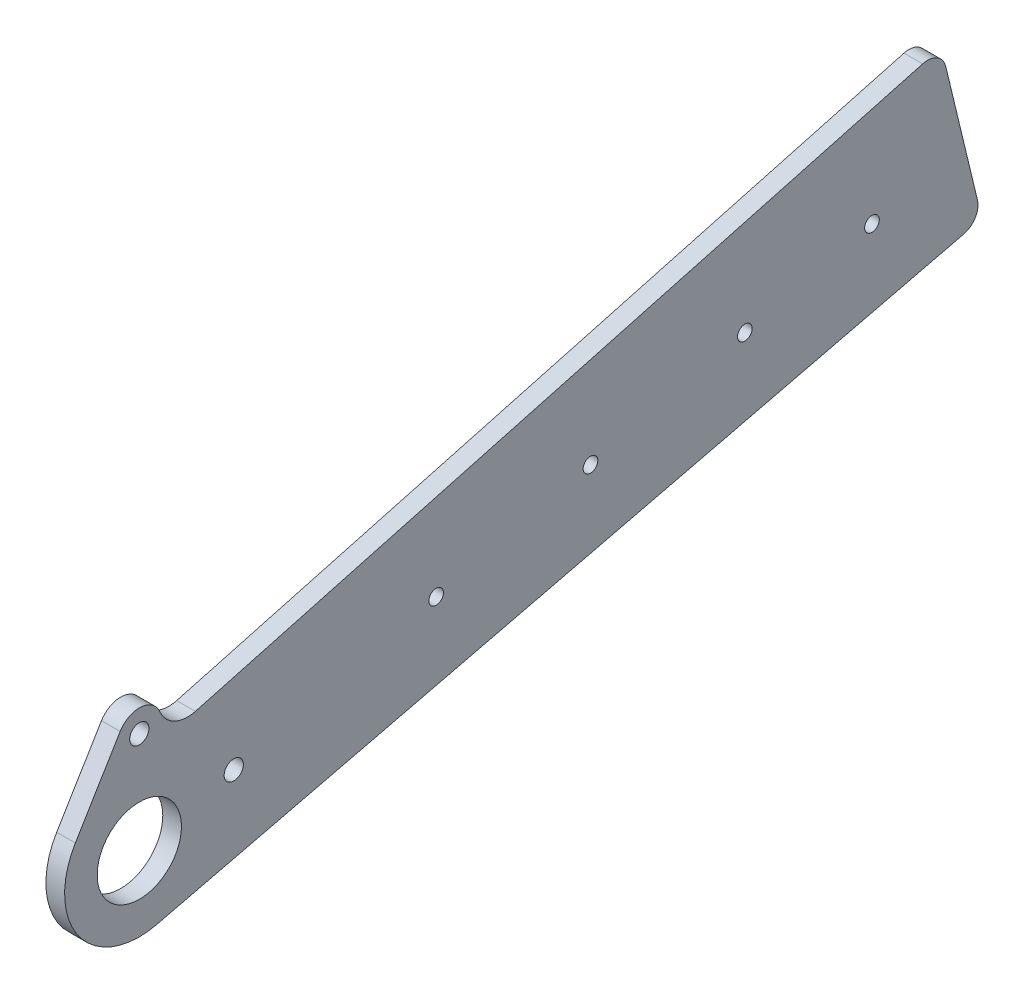
SolidWorks part; units mm, degrees
ref_plane "Alzado" through (0, 0, 0) normal (0, 0, 1) x (1, 0, 0)
ref_plane "Planta" through (0, 0, 0) normal (0, 1, 0) x (1, 0, 0)
ref_plane "Vista lateral" through (0, 0, 0) normal (1, 0, 0) x (0, 0, -1)
sketch "Croquis1" plane through (0, 0, 0) normal (0, 1, 0) x (1, 0, 0)
  line L1 (-101.6, -12.7) -> (101.6, -12.7)
  line L2 (-101.6, -12.7) -> (-101.6, 12.7)
  line L3 (-101.6, 12.7) -> (101.6, 12.7)
  line L4 (101.6, -12.7) -> (101.6, 12.7)
  line L5 (-101.6, -12.7) -> (101.6, 12.7) construction
  line L6 (-101.6, 12.7) -> (101.6, -12.7) construction
  point P0 (0, 0)
  dimension "D1" = 25.4
  dimension "D2" = 203.2
extrude "Saliente-Extruir1" add sketch "Croquis1" along normal blind 25.4
shell "Vaciado1" thickness 3.175 removed face at (-101.6, 12.7, 0) removed face at (101.6, 12.7, 0)
sketch "Croquis2" plane through (0, 25.4, 0) normal (0, 1, 0) x (1, 0, 0)
  line L0 (101.6, 12.7) -> (-101.6, 12.7) construction
  line L1 (-25.4, -12.7) -> (25.4, -12.7)
  line L2 (-25.4, -12.7) -> (-25.4, 12.7)
  line L3 (-25.4, 12.7) -> (25.4, 12.7)
  line L4 (25.4, -12.7) -> (25.4, 12.7)
  line L5 (-25.4, -12.7) -> (25.4, 12.7) construction
  line L6 (-25.4, 12.7) -> (25.4, -12.7) construction
  line L8 (-22.225, -9.525) -> (22.225, -9.525)
  line L9 (-22.225, -9.525) -> (-22.225, 9.525)
  line L10 (-22.225, 9.525) -> (22.225, 9.525)
  line L11 (22.225, -9.525) -> (22.225, 9.525)
  line L12 (-22.225, -9.525) -> (22.225, 9.525) construction
  line L13 (-22.225, 9.525) -> (22.225, -9.525) construction
  point P0 (0, 0)
  point P8 (0, 0)
  dimension "D1" = 50.8
  dimension "D2" = 3.175
  dimension "D3" = 3.175
extrude "Saliente-Extruir2" add sketch "Croquis2" along normal blind 247.65 separate body
sketch "Croquis3" plane through (0, 25.4, 0) normal (0, 1, 0) x (1, 0, 0)
  line L0 (0, 0) -> (0, 12.7) construction
  line L1 (25.4, 12.7) -> (-25.4, 12.7) construction
  circle A0 centre (-47.625, 0) radius 3.2639
  circle A1 centre (-79.375, 0) radius 3.2639
  circle A2 centre (79.375, 0) radius 3.2639
  circle A3 centre (47.625, 0) radius 3.2639
  dimension "D1" = 47.625
  dimension "D2" = 6.5278
  dimension "D3" = 31.75
extrude "Cortar-Extruir1" cut sketch "Croquis3" against normal through all
sketch "Croquis4" plane through (0, 0, 12.7) normal (0, 0, 1) x (1, 0, 0)
  line L0 (0, 25.4) -> (0, 139.6619) construction
  line L1 (-101.6, 25.4) -> (101.6, 25.4) construction
  line L2 (0, 139.6619) -> (-23.8125, 139.6619) construction
  circle A0 centre (0, 139.6619) radius 14.3129
  circle A1 centre (0, 139.6619) radius 23.8125 construction
  circle A2 centre (-23.8125, 139.6619) radius 2.4892 construction
  circle A3 centre (-11.9062, 160.2841) radius 2.4892
  circle A4 centre (11.9063, 160.2841) radius 2.4892
  circle A5 centre (23.8125, 139.6619) radius 2.4892 construction
  circle A6 centre (11.9062, 119.0397) radius 2.4892
  circle A7 centre (-11.9063, 119.0397) radius 2.4892
  dimension "D1" = 28.6258
  dimension "D3" = 47.625
  dimension "D4" = 4.9784
  dimension "D2" = 114.2619
  dimension "D6" = 23.8125
  dimension "D5" = 6
extrude "Cortar-Extruir2" cut sketch "Croquis4" against normal through all
sketch "Croquis8" plane through (0, 0, 12.7) normal (0, 0, 1) x (1, 0, 0)
  line L0 (0, 0) -> (0, 273.05) construction
  line L1 (-101.6, 12.7) -> (0, 12.7) construction
  line L2 (-101.6, 25.4) -> (-101.6, 0) construction
  line L3 (0, 12.7) -> (-12.7, 12.7) construction
  line L4 (0, 12.7) -> (12.7, 12.7) construction
  line L5 (-25.4, 273.05) -> (25.4, 273.05) construction
  line L6 (-12.7, 12.7) -> (-12.7, 25.4) construction
  circle A0 centre (0, 12.7) radius 2.4892
  circle A1 centre (-12.7, 12.7) radius 2.4892
  circle A2 centre (-25.4, 12.7) radius 2.4892
  circle A3 centre (-38.1, 12.7) radius 2.4892
  circle A4 centre (-50.8, 12.7) radius 2.4892
  circle A5 centre (0, 12.7) radius 2.4892
  circle A6 centre (-12.7, 12.7) radius 2.4892
  circle A7 centre (-25.4, 12.7) radius 2.4892
  circle A8 centre (-38.1, 12.7) radius 2.4892
  circle A9 centre (12.7, 12.7) radius 2.4892
  circle A10 centre (0, 12.7) radius 2.4892
  circle A11 centre (-12.7, 12.7) radius 2.4892
  circle A12 centre (-25.4, 12.7) radius 2.4892
  circle A13 centre (25.4, 12.7) radius 2.4892
  circle A14 centre (12.7, 12.7) radius 2.4892
  circle A15 centre (0, 12.7) radius 2.4892
  circle A16 centre (-12.7, 12.7) radius 2.4892
  circle A17 centre (38.1, 12.7) radius 2.4892
  circle A18 centre (25.4, 12.7) radius 2.4892
  circle A19 centre (12.7, 12.7) radius 2.4892
  circle A20 centre (0, 12.7) radius 2.4892
  circle A21 centre (12.7, 12.7) radius 2.4892
  circle A22 centre (25.4, 12.7) radius 2.4892
  circle A23 centre (38.1, 12.7) radius 2.4892
  circle A24 centre (50.8, 12.7) radius 2.4892
  circle A25 centre (-12.7, 25.4) radius 2.4892 [skipped]
  circle A26 centre (12.7, 25.4) radius 2.4892 [skipped]
  circle A27 centre (-12.7, 38.1) radius 2.4892
  circle A28 centre (12.7, 38.1) radius 2.4892
  circle A29 centre (-12.7, 50.8) radius 2.4892
  circle A30 centre (12.7, 50.8) radius 2.4892
  circle A31 centre (-12.7, 63.5) radius 2.4892
  circle A32 centre (12.7, 63.5) radius 2.4892
  circle A33 centre (-12.7, 76.2) radius 2.4892
  circle A34 centre (12.7, 76.2) radius 2.4892
  dimension "D1" = 4.9784
  dimension "D4" = 12.7
  dimension "D5" = 12.7
  dimension "D7" = 12.7
  dimension "D2" = 5
  dimension "D3" = 5
  dimension "D6" = 6
extrude "Cortar-Extruir4" cut sketch "Croquis8" against normal through all contours A4 | A3 | A2 | A1 | A0 | A9 | A13 | A17 | A24 | A28 | A29 | A30 | A31 | A32 | A34 | A33 | A27 region at (0, 12.7, 12.7) region at (-12.7, 12.7, 12.7) region at (-25.4, 12.7, 12.7) region at (-38.1, 12.7, 12.7) region at (-50.8, 12.7, 12.7) region at (12.7, 12.7, 12.7) region at (25.4, 12.7, 12.7) region at (38.1, 12.7, 12.7) region at (50.8, 12.7, 12.7) region at (12.7, 38.1, 12.7) region at (-12.7, 50.8, 12.7) region at (12.7, 50.8, 12.7) region at (-12.7, 63.5, 12.7) region at (12.7, 63.5, 12.7) region at (-12.7, 76.2, 12.7) region at (12.7, 76.2, 12.7)
sketch "Croquis6" plane through (0, 0, 12.7) normal (0, 0, 1) x (1, 0, 0)
  line L0 (25.4, 273.05) -> (25.4, 25.4) construction
  line L1 (-25.4, 88.646) -> (25.4, 88.646)
  line L2 (-25.4, 88.646) -> (-25.4, 114.046)
  line L3 (-25.4, 114.046) -> (25.4, 114.046)
  line L4 (25.4, 88.646) -> (25.4, 114.046)
  line L5 (-25.4, 88.646) -> (25.4, 114.046) construction
  line L6 (-25.4, 114.046) -> (25.4, 88.646) construction
  line L7 (-101.6, 25.4) -> (101.6, 25.4) construction
  line L9 (-22.225, 91.821) -> (22.225, 91.821)
  line L10 (-22.225, 91.821) -> (-22.225, 110.871)
  line L11 (-22.225, 110.871) -> (22.225, 110.871)
  line L12 (22.225, 91.821) -> (22.225, 110.871)
  line L13 (-22.225, 91.821) -> (22.225, 110.871) construction
  line L14 (-22.225, 110.871) -> (22.225, 91.821) construction
  point P0 (0, 101.346)
  point P11 (0, 101.346)
  dimension "D1" = 25.4
  dimension "D2" = 63.246
  dimension "D3" = 3.175
  dimension "D4" = 3.175
extrude "Saliente-Extruir3" add sketch "Croquis6" along normal blind 69.85 separate body
sketch "Croquis7" plane through (0, 114.046, 0) normal (0, 1, 0) x (1, 0, 0)
  line L0 (0, -12.7) -> (0, -82.55) construction
  line L1 (-25.4, -12.7) -> (25.4, -12.7) construction
  line L2 (25.4, -82.55) -> (-25.4, -82.55) construction
  line L3 (16.51, -12.7) -> (-16.51, -12.7)
  line L4 (25.4, -12.7) -> (-25.4, -12.7) construction
  line L5 (-16.51, -12.7) -> (-16.51, -34.798)
  line L6 (-13.208, -38.1) -> (13.208, -38.1)
  line L7 (16.51, -12.7) -> (16.51, -34.798)
  arc A0 (16.51, -34.798) -> (13.208, -38.1) centre (13.208, -34.798) cw
  arc A1 (-16.51, -34.798) -> (-13.208, -38.1) centre (-13.208, -34.798) ccw
  point P12 (0, -38.1)
  point P16 (16.51, -38.1)
  point P19 (-16.51, -38.1)
  dimension "D3" = 3.302
  dimension "D1" = 25.4
  dimension "D2" = 33.02
extrude "Cortar-Extruir3" cut sketch "Croquis7" against normal up to next (3.175 mm away)
sketch "Croquis11" plane through (25.4, 0, 0) normal (1, 0, 0) x (0, 0, -1)
  line L0 (0, -101.854) -> (-381, -101.854) construction
  line L1 (-82.55, 88.646) -> (-82.55, 114.046) construction
  line L2 (-82.55, 88.646) -> (-12.7, 88.646) construction
  line L6 (-517.96, -101.854) -> (-276.66, -101.854) construction
  line L7 (-517.96, -101.854) -> (-517.96, 139.446) construction
  line L8 (-517.96, 139.446) -> (-276.66, 139.446) construction
  line L9 (-276.66, -101.854) -> (-276.66, 139.446) construction
  circle A0 centre (-396.875, 145.796) radius 38.1
  dimension "D3" = 76.2
  dimension "D4" = 209.55
  dimension "D5" = 276.225
  dimension "D1" = 190.5
  dimension "D2" = 381
  dimension "D6" = 241.3
sketch "Croquis9" plane through (0, 0, 12.7) normal (0, 0, 1) x (1, 0, 0)
  line L0 (0, 0) -> (0, 273.05) construction
  line L1 (-25.4, 273.05) -> (25.4, 273.05) construction
  line L2 (50.8, 0) -> (-50.8, 0)
  line L3 (-101.6, 0) -> (101.6, 0) construction
  line L4 (-57.15, 6.35) -> (-57.15, 23.7481)
  line L5 (-101.6, 25.4) -> (101.6, 25.4) construction
  line L6 (-56.3451, 26.8425) -> (-27.2168, 79.0403)
  line L7 (-25.4, 273.05) -> (-25.4, 25.4) construction
  line L8 (-21.6717, 82.296) -> (21.6717, 82.296)
  line L9 (56.3451, 26.8425) -> (27.2168, 79.0403)
  line L10 (57.15, 6.35) -> (57.15, 23.7481)
  line L11 (-25.4, 88.646) -> (25.4, 88.646) construction
  circle A0 centre (-50.8, 12.7) radius 2.4892 construction
  arc A2 (-50.8, 0) -> (-57.15, 6.35) centre (-50.8, 6.35) cw
  arc A3 (-57.15, 23.7481) -> (-56.3451, 26.8425) centre (-50.8, 23.7481) cw
  arc A4 (-27.2168, 79.0403) -> (-21.6717, 82.296) centre (-21.6717, 75.946) cw
  arc A5 (27.2168, 79.0403) -> (21.6717, 82.296) centre (21.6717, 75.946) ccw
  arc A6 (57.15, 23.7481) -> (56.3451, 26.8425) centre (50.8, 23.7481) ccw
  arc A7 (50.8, 0) -> (57.15, 6.35) centre (50.8, 6.35) ccw
  circle A9 centre (-25.4, 12.7) radius 2.4892
  circle A10 centre (-25.4, 12.7) radius 2.4892
  circle A11 centre (-12.7, 12.7) radius 2.4892
  circle A12 centre (-12.7, 12.7) radius 2.4892
  circle A13 centre (0, 12.7) radius 2.4892
  circle A14 centre (0, 12.7) radius 2.4892
  circle A15 centre (0, 12.7) radius 2.4892
  circle A16 centre (0, 12.7) radius 2.4892
  circle A17 centre (12.7, 12.7) radius 2.4892
  circle A18 centre (12.7, 12.7) radius 2.4892
  circle A19 centre (-38.1, 12.7) radius 2.4892
  circle A20 centre (-38.1, 12.7) radius 2.4892
  circle A21 centre (-25.4, 12.7) radius 2.4892
  circle A22 centre (-25.4, 12.7) radius 2.4892
  circle A23 centre (-12.7, 12.7) radius 2.4892
  circle A24 centre (-12.7, 12.7) radius 2.4892
  circle A25 centre (0, 12.7) radius 2.4892
  circle A26 centre (0, 12.7) radius 2.4892
  circle A27 centre (-50.8, 12.7) radius 2.4892
  circle A28 centre (-50.8, 12.7) radius 2.4892
  circle A29 centre (-38.1, 12.7) radius 2.4892
  circle A30 centre (-38.1, 12.7) radius 2.4892
  circle A31 centre (25.4, 12.7) radius 2.4892
  circle A32 centre (25.4, 12.7) radius 2.4892
  circle A33 centre (38.1, 12.7) radius 2.4892
  circle A34 centre (38.1, 12.7) radius 2.4892
  circle A35 centre (-12.7, 12.7) radius 2.4892
  circle A36 centre (-12.7, 12.7) radius 2.4892
  circle A37 centre (0, 12.7) radius 2.4892
  circle A38 centre (0, 12.7) radius 2.4892
  circle A39 centre (12.7, 12.7) radius 2.4892
  circle A40 centre (12.7, 12.7) radius 2.4892
  circle A41 centre (25.4, 12.7) radius 2.4892
  circle A42 centre (25.4, 12.7) radius 2.4892
  circle A43 centre (-25.4, 12.7) radius 2.4892
  circle A44 centre (-25.4, 12.7) radius 2.4892
  circle A45 centre (-12.7, 12.7) radius 2.4892
  circle A46 centre (-12.7, 12.7) radius 2.4892
  circle A47 centre (50.8, 12.7) radius 2.4892
  circle A48 centre (50.8, 12.7) radius 2.4892
  circle A49 centre (38.1, 12.7) radius 2.4892
  circle A50 centre (38.1, 12.7) radius 2.4892
  circle A51 centre (25.4, 12.7) radius 2.4892
  circle A52 centre (25.4, 12.7) radius 2.4892
  circle A53 centre (12.7, 12.7) radius 2.4892
  circle A54 centre (12.7, 12.7) radius 2.4892
  circle A55 centre (0, 12.7) radius 2.4892
  circle A56 centre (0, 12.7) radius 2.4892
  circle A57 centre (12.7, 12.7) radius 2.4892
  circle A58 centre (12.7, 12.7) radius 2.4892
  circle A59 centre (-12.7, 76.2) radius 2.4892
  circle A60 centre (-12.7, 76.2) radius 2.4892
  circle A61 centre (12.7, 63.5) radius 2.4892
  circle A62 centre (12.7, 63.5) radius 2.4892
  circle A63 centre (-12.7, 63.5) radius 2.4892
  circle A64 centre (-12.7, 63.5) radius 2.4892
  circle A65 centre (12.7, 50.8) radius 2.4892
  circle A66 centre (12.7, 50.8) radius 2.4892
  circle A67 centre (-12.7, 50.8) radius 2.4892
  circle A68 centre (-12.7, 50.8) radius 2.4892
  circle A69 centre (12.7, 38.1) radius 2.4892
  circle A70 centre (12.7, 38.1) radius 2.4892
  circle A71 centre (-12.7, 38.1) radius 2.4892
  circle A72 centre (-12.7, 38.1) radius 2.4892
  circle A73 centre (12.7, 76.2) radius 2.4892
  circle A74 centre (12.7, 76.2) radius 2.4892
  point P22 (-57.15, 0)
  point P25 (-57.15, 25.4)
  point P28 (-25.4, 82.296)
  point P38 (0, 82.296)
  dimension "D1" = 6.35
  dimension "D3" = 6.35
  dimension "D37" = 6.35
  dimension "D4" = 0
  dimension "D5" = 0
  dimension "D6" = 0
  dimension "D7" = 0
  dimension "D8" = 0
  dimension "D9" = 0
  dimension "D10" = 0
  dimension "D11" = 0
  dimension "D12" = 0
  dimension "D13" = 0
  dimension "D14" = 0
  dimension "D15" = 0
  dimension "D16" = 0
  dimension "D17" = 0
  dimension "D18" = 0
  dimension "D19" = 0
  dimension "D20" = 0
  dimension "D21" = 0
  dimension "D22" = 0
  dimension "D23" = 0
  dimension "D24" = 0
  dimension "D25" = 0
  dimension "D26" = 0
  dimension "D27" = 0
  dimension "D28" = 0
  dimension "D29" = 0
  dimension "D30" = 0
  dimension "D31" = 0
  dimension "D32" = 0
  dimension "D33" = 0
  dimension "D34" = 0
  dimension "D35" = 0
  dimension "D36" = 0
extrude "Saliente-Extruir4" add sketch "Croquis9" along normal blind 6.35 separate body contours L0 L8 A4 L6 A3 A60 A64 A68 A72 | L0 A6 L9 A5 L8 A74 A70 A66 A62 | L0 A3 L4 A2 | L0 L2 A7 L10 A6 A56 region at (-24.3725, 36.0328, 12.7) region at (24.3725, 36.0328, 12.7)
sketch "Croquis15" plane through (25.4, 0, 0) normal (1, 0, 0) x (0, 0, -1)
  line L0 (-12.7, 0) -> (-12.7, 171.1325) construction
  line L1 (-12.7, 273.05) -> (-12.7, 25.4) construction
  line L2 (-72.5746, 227.1642) -> (-41.5317, 154.1315) construction
  line L3 (-105.4538, 208.2656) -> (-57.9713, 144.6822) construction
  line L4 (-94.6246, 238.2605) -> (-401.3483, 164.3633) construction
  line L5 (-392.4017, 127.2287) -> (-85.6779, 201.1258) construction
  line L8 (-82.55, 114.046) -> (-12.7, 114.046) construction
  circle A0 centre (-50.32, 150.396) radius 30
  arc A1 (-57.9713, 144.6822) -> (-41.5317, 154.1315) centre (-50.32, 150.396) ccw construction
  arc A2 (-401.3483, 164.3633) -> (-392.4017, 127.2287) centre (-396.875, 145.796) ccw construction
  arc A3 (-72.5746, 227.1642) -> (-105.4538, 208.2656) centre (-90.1513, 219.6932) ccw construction
  arc A4 (-85.6779, 201.1258) -> (-94.6246, 238.2605) centre (-90.1513, 219.6932) ccw construction
  dimension "D2" = 60
  dimension "D3" = 19.0986
  dimension "D4" = 38.1972
  dimension "D1" = 171.1325
  dimension "D7" = 6.35
  dimension "D8" = 7.62
sketch "Croquis16" plane through (25.4, 0, 0) normal (1, 0, 0) x (0, 0, -1)
  line L0 (-50.32, 150.396) -> (-50.32, 175.796) construction
  line L1 (-13.4332, 272.8734) -> (-118.1525, 247.644)
  line L2 (-82.55, 94.996) -> (-82.55, 113.9625)
  line L3 (-82.5522, 114.1295) -> (-83.4835, 149.5234)
  line L4 (-76.2, 88.646) -> (6.35, 88.646)
  line L5 (12.7, 273.05) -> (12.7, 25.4) construction
  line L6 (12.7, 94.996) -> (12.7, 266.7)
  line L7 (6.35, 273.05) -> (-11.9459, 273.05)
  line L8 (-94.6246, 238.2605) -> (-401.3483, 164.3633) construction
  line L9 (-122.8385, 239.9833) -> (-110.0117, 186.743)
  line L10 (-90.1513, 219.6932) -> (-116.4251, 213.3632) construction
  circle A0 centre (-90.1513, 219.6932) radius 14.3256
  circle A1 centre (-50.32, 150.396) radius 33.175
  circle A4 centre (-50.32, 150.396) radius 9.5631
  circle A5 centre (-50.32, 150.396) radius 25.4 construction
  circle A6 centre (-50.32, 175.796) radius 2.4892
  circle A7 centre (-32.3595, 168.3565) radius 2.4892 construction
  circle A8 centre (-24.92, 150.396) radius 2.4892
  circle A9 centre (-32.3595, 132.4355) radius 2.4892
  circle A10 centre (-50.32, 124.996) radius 2.4892
  circle A11 centre (-68.2805, 132.4355) radius 2.4892
  circle A12 centre (-75.72, 150.396) radius 2.4892
  circle A13 centre (-68.2805, 168.3565) radius 2.4892
  arc A18 (-105.7366, 182.1707) -> (-83.4864, 151.1506) centre (-115.2282, 151.8727) cw
  arc A19 (-110.0117, 186.743) -> (-105.7366, 182.1707) centre (-103.8383, 188.2304) ccw
  arc A21 (-118.1525, 247.644) -> (-122.8385, 239.9833) centre (-116.6652, 241.4706) ccw
  arc A23 (-11.9459, 273.05) -> (-13.4332, 272.8734) centre (-11.9459, 266.7) ccw
  circle A26 centre (-50.32, 150.396) radius 30 construction
  arc A29 (-82.55, 113.9625) -> (-82.5522, 114.1295) centre (-88.9, 113.9625) ccw
  arc A31 (12.7, 266.7) -> (6.35, 273.05) centre (6.35, 266.7) ccw
  arc A32 (6.35, 88.646) -> (12.7, 94.996) centre (6.35, 94.996) ccw
  arc A33 (-82.55, 94.996) -> (-76.2, 88.646) centre (-76.2, 94.996) ccw
  point P45 (-12.7, 273.05)
  point P72 (-82.55, 114.046)
  point P74 (12.7, 273.05)
  point P77 (12.7, 88.646)
  point P80 (-82.55, 88.646)
  dimension "D1" = 28.6512
  dimension "D2" = 3.175
  dimension "D3" = 31.75
  dimension "D4" = 19.1262
  dimension "D5" = 50.8
  dimension "D6" = 4.9784
  dimension "D9" = 6.35
  dimension "D10" = 6.35
  dimension "D14" = 6.35
  dimension "D15" = 6.35
  dimension "D12" = 6.35
  dimension "D8" = 25.4
  dimension "D11" = 12.7
  dimension "D7" = 8
extrude "Saliente-Extruir5" add sketch "Croquis16" along normal blind 6.35 separate body contours L4 A32 A31 A23 | L2 A33 L4 A23 L1 A21 L9 A19 A18 A1 L3 A29 A0 | A1 A13 A12 A11 A10 A9 A8 A6 A4 region at (25.4, 188.5949, 38.9873) region at (25.4, 182.6306, 49.9534)
sketch "Croquis12" plane through (25.4, 0, 0) normal (1, 0, 0) x (0, 0, -1)
  line L0 (-82.55, 101.346) -> (-12.7, 101.346) construction
  line L1 (-82.55, 88.646) -> (-82.55, 114.046) construction
  line L2 (-12.7, 88.646) -> (-12.7, 114.046) construction
  line L3 (0, 273.05) -> (0, 0) construction
  line L4 (-12.7, 273.05) -> (12.7, 273.05) construction
  line L5 (0, 101.346) -> (-12.7, 101.346) construction
  line L6 (0, 101.346) -> (0, 114.046) construction
  circle A1 centre (0, 101.346) radius 2.4892
  circle A2 centre (-12.7, 101.346) radius 2.4892 [skipped]
  circle A3 centre (-25.4, 101.346) radius 2.4892
  circle A4 centre (-38.1, 101.346) radius 2.4892
  circle A5 centre (-50.8, 101.346) radius 2.4892
  circle A6 centre (0, 114.046) radius 2.4892
  circle A7 centre (0, 126.746) radius 2.4892
  circle A8 centre (0, 139.446) radius 2.4892
  circle A9 centre (0, 152.146) radius 2.4892
  circle A10 centre (0, 164.846) radius 2.4892
  circle A11 centre (0, 177.546) radius 2.4892
  circle A12 centre (0, 190.246) radius 2.4892
  circle A13 centre (0, 202.946) radius 2.4892
  circle A14 centre (0, 215.646) radius 2.4892
  circle A15 centre (0, 228.346) radius 2.4892
  circle A16 centre (0, 241.046) radius 2.4892
  circle A17 centre (0, 253.746) radius 2.4892
  circle A18 centre (0, 266.446) radius 2.4892
  circle A19 centre (-63.5, 101.346) radius 2.4892
  circle A20 centre (-76.2, 101.346) radius 2.4892
  dimension "D1" = 4.9784
  dimension "D3" = 12.7
  dimension "D5" = 12.7
  dimension "D2" = 7
  dimension "D4" = 14
extrude "Cortar-Extruir5" cut sketch "Croquis12" against normal through all and the other way through all
sketch "Croquis17" plane through (31.75, 0, 0) normal (1, 0, 0) x (0, 0, -1)
  line L0 (-403.5186, 170.3118) -> (-118.2389, 247.6205)
  line L1 (-118.0654, 247.6649) -> (-21.2705, 270.9852)
  line L2 (-390.9258, 121.1026) -> (-118.1525, 186.8202)
  line L3 (-392.4017, 127.2287) -> (-85.6779, 201.1258) construction
  line L4 (-118.1525, 186.8202) -> (-112.4025, 188.2055)
  line L5 (-13.4332, 206.3797) -> (-13.4332, 264.8118)
  line L7 (-403.3993, 184.1476) -> (-418.6226, 158.9186)
  circle A0 centre (-396.875, 145.796) radius 14.3256
  circle A1 centre (-90.1513, 219.6932) radius 14.3256
  circle A2 centre (-396.875, 145.796) radius 25.4
  arc A3 (-118.2389, 247.6205) -> (-118.0654, 247.6649) centre (-116.578, 241.4916) cw
  arc A4 (-21.2705, 270.9852) -> (-13.4332, 264.8118) centre (-19.7832, 264.8118) cw
  arc A5 (-13.4332, 206.3797) -> (-43.9384, 181.4981) centre (-38.8332, 206.3797) cw
  circle A6 centre (-50.32, 150.396) radius 31.75
  arc A8 (-110.0117, 186.743) -> (-105.7366, 182.1707) centre (-103.8383, 188.2304) ccw construction
  arc A9 (-110.0117, 186.743) -> (-105.7366, 182.1707) centre (-103.8383, 188.2304) ccw
  arc A10 (-110.0117, 186.743) -> (-112.4025, 188.2055) centre (-111.9383, 186.2789) ccw
  arc A11 (-83.4864, 151.1506) -> (-105.7366, 182.1707) centre (-115.2282, 151.8727) ccw construction
  arc A12 (-89.8175, 170.9084) -> (-105.7366, 182.1707) centre (-115.2282, 151.8727) ccw
  arc A13 (-89.8175, 170.9084) -> (-74.8387, 170.5677) centre (-82.1943, 176.6192) ccw
  circle A14 centre (-396.875, 180.2108) radius 7.62
  arc A16 (-389.8471, 183.1558) -> (-377.8191, 177.2761) centre (-380.4766, 187.0824) ccw
  point P19 (-118.1525, 247.644)
  point P23 (-13.4332, 272.8734)
  dimension "D1" = 28.6512
  dimension "D2" = 50.8
  dimension "D3" = 6.35
  dimension "D4" = 63.5
  dimension "D5" = 9.525
  dimension "D6" = 25.4
  dimension "D7" = 15.24
  dimension "D8" = 34.4148
  dimension "D9" = 10.16
extrude "Saliente-Extruir6" add sketch "Croquis17" along normal blind 6.35 separate body contours A2 L2 L0 | L5 A4 A3 L0 | A2 A0 | A16 A14 L7 A2 L0 | A14 region at (31.75, 173.536, 401.4081) region at (31.75, 197.0567, 182.132) region at (31.75, 165.3985, 381.8776) region at (31.75, 180.2108, 396.875)
sketch "Croquis18" plane through (38.1, 0, 0) normal (1, 0, 0) x (0, 0, -1)
  line L0 (-122.8385, 239.9833) -> (-110.0117, 186.743) construction
  line L1 (-122.754, 239.6323) -> (-111.9631, 194.8431)
  line L2 (-403.5186, 170.3118) -> (-118.2389, 247.6205) construction
  line L3 (-403.3993, 184.1476) -> (-418.6226, 158.9186) construction
  line L5 (-403.3993, 184.1476) -> (-418.6226, 158.9186)
  line L6 (-390.9258, 121.1026) -> (-118.1525, 186.8202) construction
  line L7 (-403.5186, 170.3118) -> (-130.5882, 244.274)
  line L10 (-122.8385, 239.9833) -> (-110.0117, 186.743) construction
  line L11 (-390.9258, 121.1026) -> (-116.6492, 187.1824)
  circle A1 centre (-396.875, 145.796) radius 25.4
  circle A2 centre (-396.875, 145.796) radius 25.4
  arc A3 (-116.6492, 187.1824) -> (-111.9631, 194.8431) centre (-118.1365, 193.3558) ccw
  circle A5 centre (-396.875, 145.796) radius 14.3256
  circle A6 centre (-396.875, 145.796) radius 14.3256
  arc A12 (-122.754, 239.6323) -> (-130.5882, 244.274) centre (-128.9273, 238.145) ccw
  arc A13 (-389.8471, 183.1558) -> (-377.8191, 177.2761) centre (-380.4766, 187.0824) ccw construction
  circle A14 centre (-396.875, 180.2108) radius 7.62 construction
  arc A15 (-389.8471, 183.1558) -> (-377.8191, 177.2761) centre (-380.4766, 187.0824) ccw
  circle A16 centre (-396.875, 180.2108) radius 7.62
  point P18 (-110.4758, 188.6697)
  dimension "D2" = 6.35
  dimension "D1" = 0
  dimension "D3" = 0
extrude "Saliente-Extruir7" add sketch "Croquis18" along normal blind 6.35 from surface separate body contours L1 A12 A2 A3 | A2 | A16 A2 L7 | A16 region at (38.1, 184.7417, 244.7476) region at (38.1, 173.536, 401.4081) region at (38.1, 131.2122, 416.7871) region at (38.1, 180.2108, 396.875) starting at face at (25.4, 101.346, -2.4892)
sketch "Croquis22" plane through (38.1, 0, 0) normal (1, 0, 0) x (0, 0, -1)
  line L0 (-396.875, 145.796) -> (-90.1513, 219.6932) construction
  line L1 (-90.1513, 219.6932) -> (-50.32, 150.396) construction
  line L4 (-50.32, 236.121) -> (-37.62, 236.121) construction
  line L5 (-21.2705, 270.9852) -> (-118.0654, 247.6649) construction
  circle A0 centre (-396.875, 180.2108) radius 3.2639
  circle A1 centre (-364.7735, 153.53) radius 3.2639
  circle A2 centre (-396.875, 145.796) radius 19.0986 construction
  arc A3 (-401.3483, 164.3633) -> (-392.4017, 127.2287) centre (-396.875, 145.796) ccw construction
  circle A4 centre (-364.7735, 153.53) radius 6.35 construction
  circle A7 centre (-72.747, 189.4137) radius 3.2639
  circle A8 centre (-72.747, 189.4137) radius 6.35 construction
  circle A9 centre (-50.32, 213.896) radius 6.35 construction
  circle A10 centre (-50.32, 213.896) radius 3.2639
  circle A13 centre (-37.62, 236.121) radius 3.2639
  circle A14 centre (-37.62, 236.121) radius 6.35 construction
  circle A15 centre (-72.747, 252.0515) radius 3.2639
  circle A16 centre (-72.747, 252.0515) radius 6.35 construction
  circle A17 centre (-19.7832, 264.8118) radius 6.35 construction
  circle A18 centre (-19.7832, 264.8118) radius 3.2639
  dimension "D1" = 6.5278
  dimension "D2" = 33.02
  dimension "D3" = 12.7
  dimension "D4" = 34.925
  dimension "D5" = 63.5
  dimension "D6" = 22.225
  dimension "D7" = 12.7
extrude "Cortar-Extruir6" cut sketch "Croquis22" against normal through all
sketch "Croquis24" plane through (38.1, 0, 0) normal (1, 0, 0) x (0, 0, -1)
  line L0 (-396.875, 145.796) -> (-90.1513, 219.6932) construction
  line L1 (-243.5131, 182.7446) -> (-247.9864, 201.3119) construction
  line L2 (-94.6246, 238.2605) -> (-401.3483, 164.3633) construction
  circle A0 centre (-295.9867, 170.1024) radius 2.4892
  circle A1 centre (-191.0395, 195.3867) radius 2.4892
  circle A2 centre (-243.5131, 182.7446) radius 2.4892
  circle A3 centre (-147.826, 205.7979) radius 2.4892
  dimension "D1" = 4.9784
  dimension "D2" = 53.975
  dimension "D3" = 44.45
sketch "Croquis25" plane through (31.75, 0, 0) normal (1, 0, 0) x (0, 0, -1)
  line L0 (-12.7, 0) -> (-12.7, 139.7) construction
  line L1 (-12.7, 123.825) -> (-12.7, 155.575)
  line L2 (-12.7, 0) -> (-12.7, 171.1325) construction
  line L3 (-15.875, 158.75) -> (-17.145, 158.75)
  line L4 (-20.32, 155.575) -> (-20.32, 123.825)
  line L5 (-12.7, 139.7) -> (-20.32, 139.7) construction
  line L6 (-15.875, 120.65) -> (-17.145, 120.65)
  arc A0 (-12.7, 155.575) -> (-15.875, 158.75) centre (-15.875, 155.575) ccw
  arc A1 (-15.875, 120.65) -> (-12.7, 123.825) centre (-15.875, 123.825) ccw
  arc A2 (-17.145, 120.65) -> (-20.32, 123.825) centre (-17.145, 123.825) cw
  arc A3 (-17.145, 158.75) -> (-20.32, 155.575) centre (-17.145, 155.575) ccw
  point P13 (-12.7, 158.75)
  point P16 (-12.7, 120.65)
  point P19 (-20.32, 120.65)
  point P22 (-20.32, 158.75)
  dimension "D4" = 3.175
  dimension "D1" = 139.7
  dimension "D2" = 7.62
  dimension "D3" = 38.1
extrude "Cortar-Extruir8" cut sketch "Croquis25" against normal through all
extrude "Cortar-Extruir9" cut sketch "Croquis24" against normal through all
delete or keep bodies "Sólido-Eliminar/Conservar 1" [suppressed] type keep bodies bodies 112
delete or keep bodies "Sólido-Eliminar/Conservar 2" [suppressed] type keep bodies bodies 111
delete or keep bodies "Sólido-Eliminar/Conservar 3" [suppressed] type keep bodies bodies 107
delete or keep bodies "Sólido-Eliminar/Conservar 4" [suppressed] type keep bodies bodies 109
delete or keep bodies "Sólido-Eliminar/Conservar 5" [suppressed] type keep bodies bodies 121
delete or keep bodies "Sólido-Eliminar/Conservar 6" [suppressed] type keep bodies bodies 125
sketch "Croquis29" plane through (0, 0, 0) normal (1, 0, 0) x (0, 0, -1)
  line L0 (-392.4017, 127.2287) -> (-85.6779, 201.1258) construction
  line L1 (-94.6246, 238.2605) -> (-401.3483, 164.3633) construction
  line L2 (-392.4017, 127.2287) -> (-85.6779, 201.1258) construction
  line L3 (-94.6246, 238.2605) -> (-401.3483, 164.3633) construction
  line L4 (-392.8842, 129.2314) -> (-86.1604, 203.1285)
  line L5 (-94.1421, 236.2578) -> (-400.8658, 162.3606)
  line L6 (-391.9941, 125.5371) -> (-85.2704, 199.4342)
  line L7 (-95.0321, 239.9521) -> (-401.7559, 166.0549)
  arc A0 (-85.6779, 201.1258) -> (-94.6246, 238.2605) centre (-90.1513, 219.6932) ccw construction
  arc A1 (-401.3483, 164.3633) -> (-392.4017, 127.2287) centre (-396.875, 145.796) ccw construction
  arc A2 (-85.6779, 201.1258) -> (-94.6246, 238.2605) centre (-90.1513, 219.6932) ccw construction
  arc A3 (-401.3483, 164.3633) -> (-392.4017, 127.2287) centre (-396.875, 145.796) ccw construction
  arc A4 (-86.1604, 203.1285) -> (-94.1421, 236.2578) centre (-90.1513, 219.6932) ccw
  arc A5 (-400.8658, 162.3606) -> (-392.8842, 129.2314) centre (-396.875, 145.796) ccw
  arc A6 (-401.7559, 166.0549) -> (-391.9941, 125.5371) centre (-396.875, 145.796) ccw
  arc A7 (-85.2704, 199.4342) -> (-95.0321, 239.9521) centre (-90.1513, 219.6932) ccw
  dimension "D1" = 2.06
  dimension "D2" = 3.8
extrude "Saliente-Extruir9" add sketch "Croquis29" along normal mid plane 9 separate body
sketch "Croquis30" plane through (0, 0, 0) normal (1, 0, 0) x (0, 0, -1)
  line L0 (-72.5746, 227.1642) -> (-41.5317, 154.1315) construction
  line L1 (-105.4538, 208.2656) -> (-57.9713, 144.6822) construction
  line L2 (-72.5746, 227.1642) -> (-41.5317, 154.1315) construction
  line L3 (-105.4538, 208.2656) -> (-57.9713, 144.6822) construction
  line L4 (-74.4704, 226.3584) -> (-43.4275, 153.3257)
  line L5 (-103.8032, 209.4982) -> (-56.3207, 145.9148)
  line L6 (-106.8479, 207.2245) -> (-59.3654, 143.6411)
  line L7 (-70.9732, 227.8449) -> (-39.9303, 154.8122)
  arc A0 (-57.9713, 144.6822) -> (-41.5317, 154.1315) centre (-50.32, 150.396) ccw construction
  arc A1 (-72.5746, 227.1642) -> (-105.4538, 208.2656) centre (-90.1513, 219.6932) ccw construction
  arc A2 (-57.9713, 144.6822) -> (-41.5317, 154.1315) centre (-50.32, 150.396) ccw construction
  arc A3 (-72.5746, 227.1642) -> (-105.4538, 208.2656) centre (-90.1513, 219.6932) ccw construction
  arc A4 (-56.3207, 145.9148) -> (-43.4275, 153.3257) centre (-50.32, 150.396) ccw
  arc A5 (-74.4704, 226.3584) -> (-103.8032, 209.4982) centre (-90.1513, 219.6932) ccw
  arc A6 (-70.9732, 227.8449) -> (-106.8479, 207.2245) centre (-90.1513, 219.6932) ccw
  arc A7 (-59.3654, 143.6411) -> (-39.9303, 154.8122) centre (-50.32, 150.396) ccw
  dimension "D1" = 2.06
  dimension "D2" = 3.8
extrude "Saliente-Extruir10" add sketch "Croquis30" along normal mid plane 15 separate body
delete or keep bodies "Sólido-Eliminar/Conservar 7" [suppressed] type keep bodies bodies 123
delete or keep bodies "Sólido-Eliminar/Conservar 8" [suppressed] type keep bodies bodies 124
delete or keep bodies "Sólido-Eliminar/Conservar 9" type keep bodies bodies 126
equation "\"D1@Croquis15\"=5.5500+1.1875pulgadas"
equation "\"D3@Croquis15\"=(12*5mm)/pi"
equation "\"D4@Croquis15\"=(24*5mm)/pi"
equation "\"D5@Croquis15\"=(50*5mm)+1mm"
equation "\"D6@Croquis15\"=(150*5mm)+1mm"
